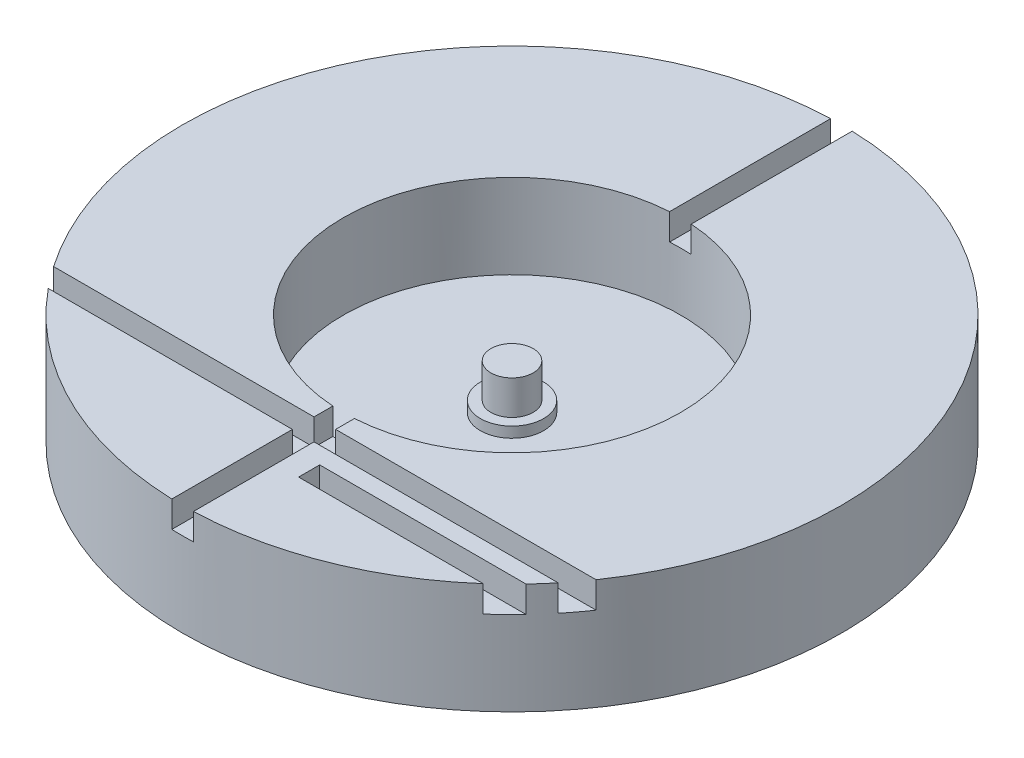
SolidWorks part; units mm, degrees
material "Cast Alloy Steel"
ref_plane "Front Plane" through (0, 0, 0) normal (0, 0, 1) x (1, 0, 0)
ref_plane "Top Plane" through (0, 0, 0) normal (0, 1, 0) x (1, 0, 0)
ref_plane "Right Plane" through (0, 0, 0) normal (1, 0, 0) x (0, 0, -1)
sketch "Sketch1" plane through (0, 0, 0) normal (0, 1, 0) x (1, 0, 0)
  circle A0 centre (0, 0) radius 62.5
  dimension "D1" = 125
extrude "Boss-Extrude1" add sketch "Sketch1" along normal blind 21
sketch "Sketch2" plane through (0, 21, 0) normal (0, 1, 0) x (1, 0, 0)
  circle A0 centre (0, 0) radius 32
  circle A1 centre (0, 0) radius 6
  dimension "D1" = 64
extrude "Cut-Extrude1" cut sketch "Sketch2" against normal blind 16
sketch "Sketch3" plane through (0, 21, 0) normal (0, 1, 0) x (1, 0, 0)
  circle A0 centre (0, 0) radius 6
  circle A1 centre (0, 0) radius 4
extrude "Cut-Extrude2" cut sketch "Sketch3" against normal blind 14
sketch "Sketch4" plane through (0, 21, 0) normal (0, 1, 0) x (1, 0, 0)
  circle A0 centre (0, 0) radius 4
extrude "Cut-Extrude3" cut sketch "Sketch4" against normal blind 7.5
sketch "Sketch5" plane through (0, 21, 0) normal (0, 1, 0) x (1, 0, 0)
  line L0 (0, 0) -> (2.05, 0) construction
  line L1 (0, 0) -> (-2.05, 0) construction
  line L2 (2.05, 62.4664) -> (2.05, -62.4664)
  line L3 (-2.05, 62.4664) -> (-2.05, -62.4664)
  circle A0 centre (0, 0) radius 62.5 construction
  arc A1 (-2.05, -62.4664) -> (2.05, -62.4664) centre (0, 0) ccw
  arc A2 (2.05, 62.4664) -> (-2.05, 62.4664) centre (0, 0) ccw
  dimension "D1" = 2.05
  dimension "D2" = 2.05
extrude "Cut-Extrude4" cut sketch "Sketch5" against normal blind 5
sketch "Sketch6" plane through (0, 21, 0) normal (0, 1, 0) x (1, 0, 0)
  line L0 (0, 0) -> (0, -37.5) construction
  line L2 (-48.35, -39.6046) -> (48.35, -39.6046)
  line L4 (-51.4393, -35.5) -> (51.4393, -35.5)
  line L6 (-48.5276, -39.3868) -> (51.4393, -35.5) construction
  line L7 (-51.4393, -35.5) -> (48.5276, -39.3868) construction
  arc A0 (2.05, -62.4664) -> (2.05, 62.4664) centre (0, 0) ccw construction
  arc A1 (-51.4393, -35.5) -> (-48.35, -39.6046) centre (0, 0) ccw
  arc A2 (48.35, -39.6046) -> (51.4393, -35.5) centre (0, 0) ccw
  dimension "D1" = 37.5
  dimension "D2" = 96.7
  dimension "D3" = 102.8786
extrude "Cut-Extrude5" cut sketch "Sketch6" against normal blind 5
sketch "Sketch9" plane through (0, 21, 0) normal (0, 1, 0) x (1, 0, 0)
  line L0 (0, 0) -> (0, -45) construction
  line L1 (0, -45) -> (43.3734, -45) construction
  line L2 (47.1162, -42.8483) -> (45.5003, -42.8483)
  line L3 (6.3701, -42.8483) -> (47.1162, -42.8483)
  line L4 (6.3701, -42.8483) -> (6.3701, -46.8483)
  line L5 (6.3701, -46.8483) -> (41.3701, -46.8483)
  line L6 (41.3701, -45) -> (41.3701, -46.8483)
  line L7 (6.3701, -42.8483) -> (41.3701, -46.8483) construction
  line L8 (6.3701, -46.8483) -> (47.1162, -42.8483) construction
  arc A0 (41.3701, -46.8483) -> (45.5003, -42.8483) centre (0, 0) ccw
  arc A1 (2.05, -62.4664) -> (48.35, -39.6046) centre (0, 0) ccw construction
  point P3 (25.1977, -45)
  arc M7 (2.05, -62.4664) -> (48.35, -39.6046) centre (0, 0) ccw
  dimension "D1" = 45
  dimension "D2" = 35
  dimension "D3" = 4
  dimension "D4" = 25.1977
extrude "Cut-Extrude6" cut sketch "Sketch9" against normal blind 5 contours L4 L5 L2 L3 M7 region at (24.9535, 21, 44.8112)
